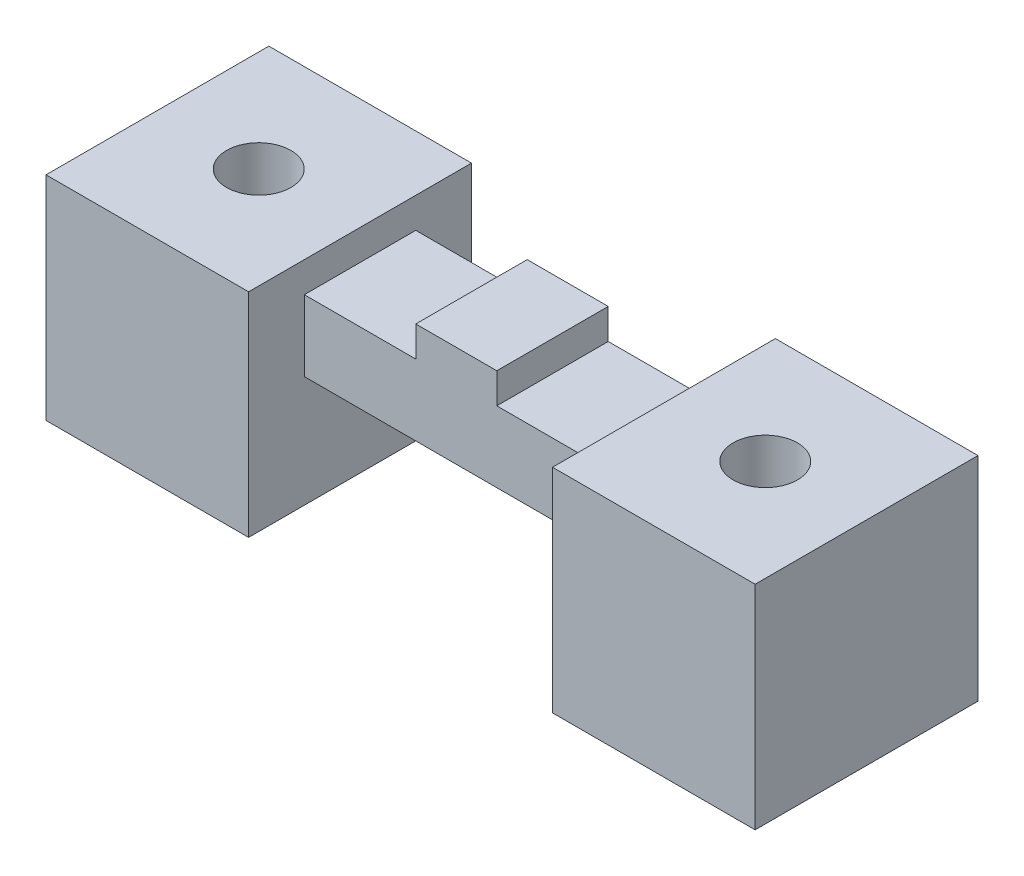
SolidWorks part; units mm, degrees
ref_plane "Front Plane" through (0, 0, 0) normal (0, 0, 1) x (1, 0, 0)
ref_plane "Top Plane" through (0, 0, 0) normal (0, 1, 0) x (1, 0, 0)
ref_plane "Right Plane" through (0, 0, 0) normal (1, 0, 0) x (0, 0, -1)
sketch "Sketch1" plane through (0, 0, 0) normal (0, 1, 0) x (1, 0, 0)
  line L1 (-35, -11) -> (35, -11)
  line L2 (-35, -11) -> (-35, 11)
  line L3 (-35, 11) -> (35, 11)
  line L4 (35, -11) -> (35, 11)
  line L5 (-35, -11) -> (35, 11) construction
  line L6 (-35, 11) -> (35, -11) construction
  point P0 (0, 0)
  dimension "D1" = 70
  dimension "D2" = 22
extrude "Boss-Extrude1" add sketch "Sketch1" against normal blind 21
sketch "Sketch2" plane through (0, -21, 0) normal (0, -1, 0) x (1, 0, 0)
  line L0 (0, 11) -> (0, -11) construction
  line L1 (-35, 11) -> (35, 11) construction
  line L2 (35, -11) -> (-35, -11) construction
  line L4 (-15, 11) -> (15, 11)
  line L5 (-15, 11) -> (-15, -11)
  line L6 (-15, -11) -> (15, -11)
  line L7 (15, 11) -> (15, -11)
  line L8 (-15, 11) -> (15, -11) construction
  line L9 (-15, -11) -> (15, 11) construction
  point P6 (0, 0)
  line M5 (35, 11) -> (-35, 11)
  line M7 (-35, -11) -> (35, -11)
  dimension "D1" = 30
extrude "Cut-Extrude2" cut sketch "Sketch2" against normal blind 11 contours L7 L5 M5 M7 region at (0, -21, 0)
sketch "Sketch3" plane through (0, -21, 0) normal (0, -1, 0) x (1, 0, 0)
  line L0 (0, 0) -> (0, -11) construction
  line L1 (-15, -11) -> (15, -11) construction
  circle A0 centre (-25, 0) radius 3.175
  circle A1 centre (25, 0) radius 3.175
  dimension "D2" = 6.35
  dimension "D1" = 25
extrude "Cut-Extrude3" cut sketch "Sketch3" against normal blind 22
sketch "Sketch4" plane through (0, 0, 0) normal (0, 1, 0) x (1, 0, 0)
  line L1 (15, 5.5) -> (-15, 5.5)
  line L2 (15, 5.5) -> (15, 11)
  line L3 (15, 11) -> (-15, 11)
  line L4 (-15, 5.5) -> (-15, 11)
  line L5 (15, 5.5) -> (-15, 11) construction
  line L6 (15, 11) -> (-15, 5.5) construction
  line L7 (35, 11) -> (-35, 11) construction
  line L8 (0, 8.25) -> (0, 2.3629) construction
  line L9 (-11.7158, 0) -> (10.0734, 0) construction
  line L10 (15, -11) -> (-15, -5.5) construction
  line L11 (15, -5.5) -> (-15, -11) construction
  line L12 (-15, -5.5) -> (-15, -11)
  line L13 (15, -11) -> (-15, -11)
  line L14 (15, -5.5) -> (15, -11)
  line L15 (15, -5.5) -> (-15, -5.5)
  point P0 (0, 0)
  dimension "D1" = 30
  dimension "D2" = 5.5
extrude "Cut-Extrude4" cut sketch "Sketch4" against normal blind 11
sketch "Sketch5" plane through (0, 0, 0) normal (0, 1, 0) x (1, 0, 0)
  line L0 (15, -5.5) -> (-15, -5.5) construction
  line L1 (-15, 5.5) -> (-4, 5.5)
  line L2 (-15, 5.5) -> (-15, -5.5)
  line L3 (-15, -5.5) -> (-4, -5.5)
  line L4 (-4, 5.5) -> (-4, -5.5)
  line L5 (0, 0) -> (0, -5.5) construction
  line L6 (15, -5.5) -> (-15, -5.5) construction
  line L7 (4, 5.5) -> (4, -5.5)
  line L8 (15, -5.5) -> (4, -5.5)
  line L9 (15, 5.5) -> (15, -5.5)
  line L10 (15, 5.5) -> (4, 5.5)
  dimension "D1" = 11
extrude "Cut-Extrude5" cut sketch "Sketch5" against normal blind 3
